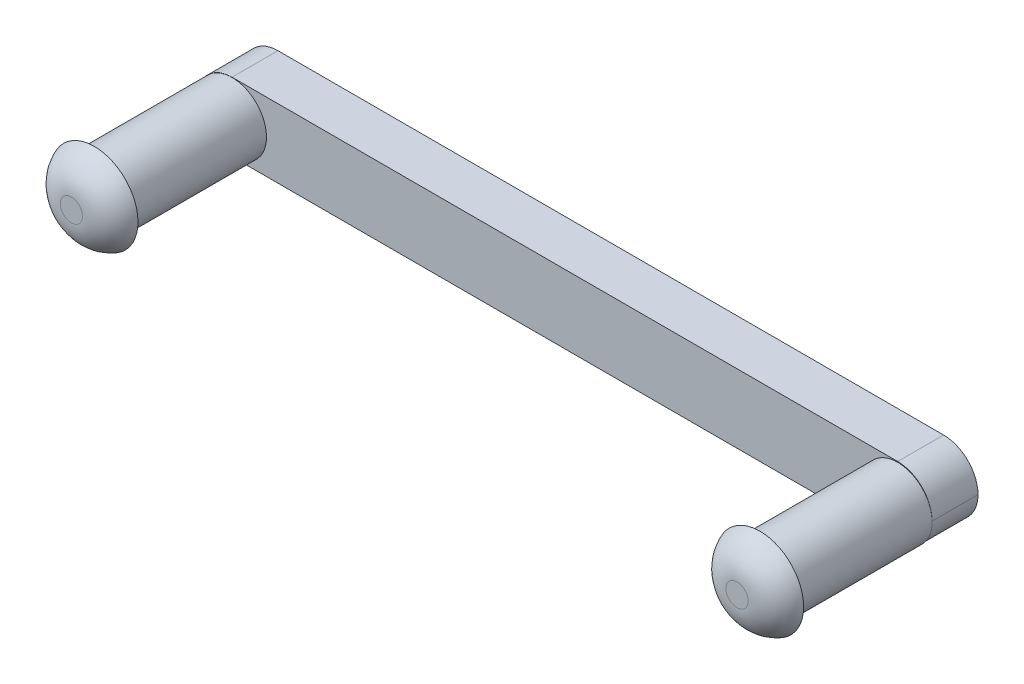
SolidWorks part; units mm, degrees
ref_plane "Plan de face" through (0, 0, 0) normal (0, 0, 1) x (1, 0, 0)
ref_plane "Plan de dessus" through (0, 0, 0) normal (0, 1, 0) x (1, 0, 0)
ref_plane "Plan de droite" through (0, 0, 0) normal (1, 0, 0) x (0, 0, -1)
sketch "Esquisse1" plane through (-13.7055, 0.6484, 0) normal (0, 0, 1) x (1, 0, 0)
  line L1 (31.2158, 14.183) -> (63.2158, 14.183)
  line L2 (31.2158, 14.183) -> (31.2158, 11.183)
  line L3 (31.2158, 11.183) -> (63.2158, 11.183)
  line L4 (63.2158, 14.183) -> (63.2158, 11.183)
  dimension "D1" = 32
  dimension "D2" = 3
extrude "Boss.-Extru.2" add sketch "Esquisse1" along normal blind 2
sketch "Esquisse4" plane through (-13.7055, 4.052, 2) normal (0, 0, 1) x (1, 0, 0)
  circle A0 centre (32.7169, 9.2695) radius 1.5
  circle A1 centre (61.7169, 9.2504) radius 1.5
  dimension "D2" = 3
  dimension "D3" = 3
  dimension "D1" = 29
extrude "Boss.-Extru.3" add sketch "Esquisse4" along normal blind 6
sketch "Esquisse5" plane through (-13.7055, 4.052, 8) normal (0, 0, 1) x (1, 0, 0)
  circle A2 centre (32.7169, 9.2695) radius 1.9
  circle A3 centre (32.7169, 9.2695) radius 1.9
  circle A5 centre (61.7169, 9.2504) radius 1.9
  circle A6 centre (61.7169, 9.2504) radius 1.9
  dimension "D1" = 0.4
  dimension "D2" = 0.4
extrude "Boss.-Extru.4" add sketch "Esquisse5" along normal blind 1
fillet "Congé13" radius 1.5 2 edges at (49.5103, 14.8315, 1) (49.5103, 11.8315, 1)
fillet "Congé14" radius 1.5 2 edges at (17.5103, 11.8315, 1) (17.5103, 14.8315, 1)
fillet "Congé16" radius 1.5 1 edges at (49.9114, 13.3024, 9)
fillet "Congé17" radius 1.5 1 edges at (20.9114, 13.3215, 9)
